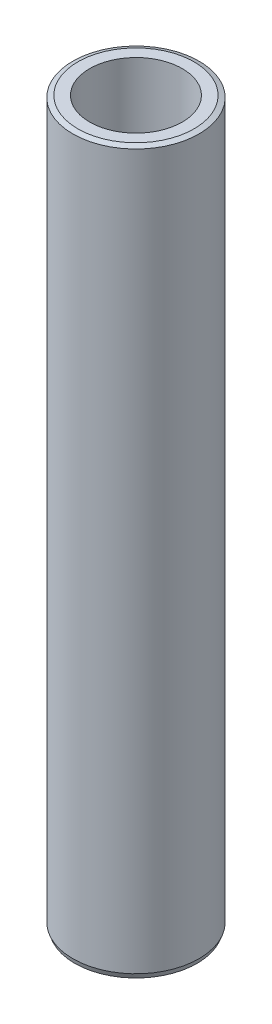
SolidWorks part; units mm, degrees
ref_plane "Front Plane" through (0, 0, 0) normal (0, 0, 1) x (1, 0, 0)
ref_plane "Top Plane" through (0, 0, 0) normal (0, 1, 0) x (1, 0, 0)
ref_plane "Right Plane" through (0, 0, 0) normal (1, 0, 0) x (0, 0, -1)
sketch "Sketch1" plane through (0, 0, 0) normal (0, 1, 0) x (1, 0, 0)
  circle A0 centre (0, 0) radius 52.5
  dimension "SHAFT_OD" = 105
extrude "Boss-Extrude1" add sketch "Sketch1" along normal blind 600
sketch "Sketch2" plane through (0, 0, 0) normal (0, 1, 0) x (1, 0, 0)
  circle A0 centre (0, 0) radius 38.5579
  dimension "BORE_D" = 77.1158
extrude "Cut-Extrude1" cut sketch "Sketch2" along normal through all
chamfer "Chamfer1" distance 1.574 angle 69.285 2 edges at (0, 600, 52.5) (0, 0, 52.5) first distance on face at (0, 600, 52.5) first distance on face at (0, 0, 38.5579)
